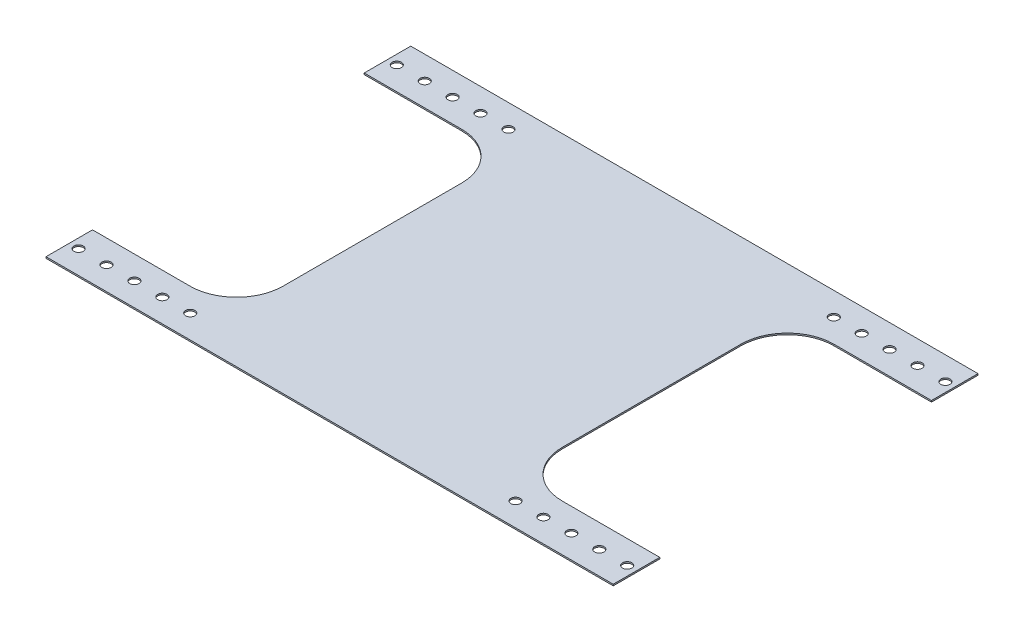
SolidWorks part; units mm, degrees
ref_plane "Front Plane" through (0, 0, 0) normal (0, 0, 1) x (1, 0, 0)
ref_plane "Top Plane" through (0, 0, 0) normal (0, 1, 0) x (1, 0, 0)
ref_plane "Right Plane" through (0, 0, 0) normal (1, 0, 0) x (0, 0, -1)
sketch "Sketch3" plane through (0, 0, 0) normal (0, 1, 0) x (1, 0, 0)
  line L0 (-152.4, 98) -> (152.4, 98)
  line L1 (-152.4, 98) -> (-152.4, 73)
  line L2 (-152.4, 73) -> (-100, 73)
  line L3 (-75, 48) -> (-75, -48)
  line L4 (0, 0) -> (-261.7187, 0) construction
  line L5 (0, 0) -> (0, 124.0234) construction
  line L6 (75, 48) -> (75, -48)
  line L7 (152.4, 73) -> (100, 73)
  line L8 (152.4, 98) -> (152.4, 73)
  line L9 (152.4, -98) -> (152.4, -73)
  line L10 (152.4, -73) -> (100, -73)
  line L11 (-152.4, -73) -> (-100, -73)
  line L12 (-152.4, -98) -> (-152.4, -73)
  line L13 (-152.4, -98) -> (152.4, -98)
  line L14 (152.4, -85.5) -> (-152.4, -85.5) construction
  line L15 (152.4, 85.5) -> (-152.4, 85.5) construction
  arc A0 (75, 48) -> (100, 73) centre (100, 48) cw
  arc A1 (100, -73) -> (75, -48) centre (100, -48) cw
  arc A2 (-100, -73) -> (-75, -48) centre (-100, -48) ccw
  arc A3 (-100, 73) -> (-75, 48) centre (-100, 48) cw
  point P13 (0, 98)
  point P16 (75, 0)
  point P17 (-75, 0)
  point P21 (75, 73)
  point P24 (75, -73)
  point P27 (-75, -73)
  point P30 (-75, 73)
  dimension "D5" = 25
  dimension "D1" = 25
  dimension "D4" = 150
  dimension "D2" = 304.8
  dimension "D3" = 171
extrude "Sheet" add sketch "Sketch3" along normal blind 0.7937
sketch "Sketch4" plane through (0, 0.7937, 0) normal (0, 1, 0) x (1, 0, 0)
  line L0 (-152.4, 85.5) -> (-75, 85.5) construction
  line L1 (-152.4, 98) -> (-152.4, 73) construction
  line L2 (-75, 48) -> (-75, -48) construction
  circle A0 centre (-147.4, 85.5) radius 2.5
  circle A1 centre (-132.4, 85.5) radius 2.5
  circle A2 centre (-117.4, 85.5) radius 2.5
  circle A3 centre (-102.4, 85.5) radius 2.5
  circle A4 centre (-87.4, 85.5) radius 2.5
  dimension "D1" = 5
  dimension "D2" = 5
  dimension "D4" = 15
  dimension "D3" = 5
extrude "MountHoles" cut sketch "Sketch4" against normal through all
mirror "Mirror3" about plane through (0, 0, 0) normal (0, 0, 1) of "MountHoles"
mirror "Mirror4" about plane through (0, 0, 0) normal (1, 0, 0) of "Mirror3"
ref_plane "HoleAlignment" through (0, 0, 85.5) normal (0, 0, 1) x (1, 0, 0)
equation "\"SheetLength\"=304.8"
equation "\"D2@Sketch3\"=\"SheetLength\""
